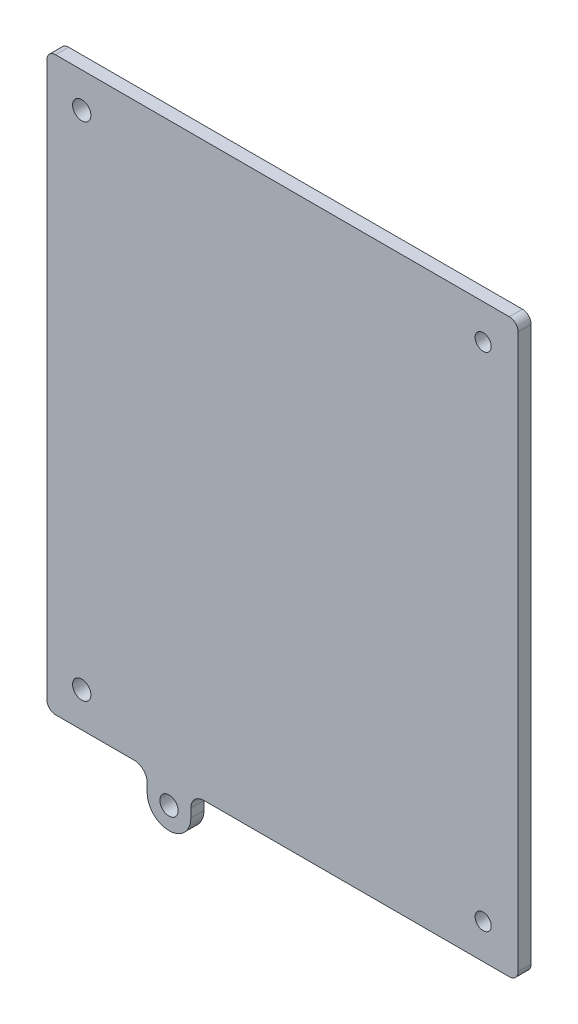
SolidWorks part; units mm, degrees
material "6061-T6 Black anodised"
ref_plane "Front Plane" through (0, 0, 0) normal (0, 0, 1) x (1, 0, 0)
ref_plane "Top Plane" through (0, 0, 0) normal (0, 1, 0) x (1, 0, 0)
ref_plane "Right Plane" through (0, 0, 0) normal (1, 0, 0) x (0, 0, -1)
sketch "Model" plane through (0, 0, 0) normal (0, 0, 1) x (1, 0, 0)
  line L0 (104.1673, 32.1811) -> (4.1672, 32.1811)
  line L1 (104.1673, 155.1806) -> (104.1673, 32.1811)
  line L2 (4.1672, 155.1806) -> (104.1673, 155.1806)
  line L3 (4.1672, 32.1811) -> (4.1672, 155.1806)
  line L4 (44.9158, 146.4259) -> (47.4224, 146.4259)
  line L5 (47.4224, 146.4259) -> (47.4224, 148.9326)
  line L6 (47.4224, 148.9326) -> (44.9158, 148.9326)
  line L7 (44.9158, 148.9326) -> (44.9158, 146.4259)
  line L8 (77.4127, 147.4278) -> (79.9193, 147.4278)
  line L9 (79.9193, 147.4278) -> (79.9193, 149.9344)
  line L10 (79.9193, 149.9344) -> (77.4127, 149.9344)
  line L11 (77.4127, 149.9344) -> (77.4127, 147.4278)
  line L12 (6.3266, 141.9721) -> (8.3592, 141.9721)
  line L13 (8.3592, 141.9721) -> (8.3592, 144.0047)
  line L14 (8.3592, 144.0047) -> (6.3266, 144.0047)
  line L15 (6.3266, 144.0047) -> (6.3266, 141.9721)
  line L16 (6.3266, 121.6529) -> (8.3592, 121.6529)
  line L17 (8.3592, 121.6529) -> (8.3592, 123.6855)
  line L18 (8.3592, 123.6855) -> (6.3266, 123.6855)
  line L19 (6.3266, 123.6855) -> (6.3266, 121.6529)
  line L20 (6.3266, 101.3324) -> (8.3592, 101.3324)
  line L21 (8.3592, 101.3324) -> (8.3592, 103.365)
  line L22 (8.3592, 103.365) -> (6.3266, 103.365)
  line L23 (6.3266, 103.365) -> (6.3266, 101.3324)
  line L24 (6.3266, 81.0118) -> (8.3592, 81.0118)
  line L25 (8.3592, 81.0118) -> (8.3592, 83.0444)
  line L26 (8.3592, 83.0444) -> (6.3266, 83.0444)
  line L27 (6.3266, 83.0444) -> (6.3266, 81.0118)
  line L28 (6.3266, 60.6927) -> (8.3592, 60.6927)
  line L29 (8.3592, 60.6927) -> (8.3592, 62.7253)
  line L30 (8.3592, 62.7253) -> (6.3266, 62.7253)
  line L31 (6.3266, 62.7253) -> (6.3266, 60.6927)
  line L32 (85.9221, 148.4144) -> (87.9547, 148.4144)
  line L33 (87.9547, 148.4144) -> (87.9547, 150.447)
  line L34 (87.9547, 150.447) -> (85.9221, 150.447)
  line L35 (85.9221, 150.447) -> (85.9221, 148.4144)
  line L36 (6.3266, 50.5324) -> (8.3592, 50.5324)
  line L37 (8.3592, 50.5324) -> (8.3592, 52.565)
  line L38 (8.3592, 52.565) -> (6.3266, 52.565)
  line L39 (6.3266, 52.565) -> (6.3266, 50.5324)
  line L40 (6.3266, 42.9118) -> (8.3592, 42.9118)
  line L41 (8.3592, 42.9118) -> (8.3592, 44.9444)
  line L42 (8.3592, 44.9444) -> (6.3266, 44.9444)
  line L43 (6.3266, 44.9444) -> (6.3266, 42.9118)
  line L44 (52.8726, 50.0418) -> (54.3815, 50.0418)
  line L45 (54.3815, 50.0418) -> (54.3815, 51.5508)
  line L46 (54.3815, 51.5508) -> (52.8726, 51.5508)
  line L47 (52.8726, 51.5508) -> (52.8726, 50.0418)
  line L48 (58.4219, 130.1637) -> (60.4545, 130.1637)
  line L49 (60.4545, 130.1637) -> (60.4545, 132.1963)
  line L50 (60.4545, 132.1963) -> (58.4219, 132.1963)
  line L51 (58.4219, 132.1963) -> (58.4219, 130.1637)
  line L52 (97.8807, 141.1439) -> (99.9133, 141.1439)
  line L53 (99.9133, 141.1439) -> (99.9133, 143.1765)
  line L54 (99.9133, 143.1765) -> (97.8807, 143.1765)
  line L55 (97.8807, 143.1765) -> (97.8807, 141.1439)
  line L56 (48.438, 37.3046) -> (48.438, 37.0552)
  line L57 (49.9456, 37.0552) -> (49.9456, 37.3046)
  line L58 (52.8877, 37.3046) -> (52.8877, 37.0552)
  line L59 (54.3967, 37.0552) -> (54.3967, 37.3046)
  line L60 (54.3126, 34.0993) -> (54.3126, 33.8995)
  line L61 (56.7201, 33.8995) -> (56.7201, 34.0993)
  line L62 (46.1133, 34.0993) -> (46.1133, 33.8995)
  line L63 (48.5207, 33.8995) -> (48.5207, 34.0993)
  line L64 (82.9607, 49.0165) -> (84.9933, 49.0165)
  line L65 (84.9933, 49.0165) -> (84.9933, 51.0492)
  line L66 (84.9933, 51.0492) -> (82.9607, 51.0492)
  line L67 (82.9607, 51.0492) -> (82.9607, 49.0165)
  line L68 (29.8828, 70.9163) -> (31.9154, 70.9163)
  line L69 (31.9154, 70.9163) -> (31.9154, 72.9489)
  line L70 (31.9154, 72.9489) -> (29.8828, 72.9489)
  line L71 (29.8828, 72.9489) -> (29.8828, 70.9163)
  line L72 (29.8828, 68.1658) -> (31.9154, 68.1658)
  line L73 (31.9154, 68.1658) -> (31.9154, 70.1984)
  line L74 (31.9154, 70.1984) -> (29.8828, 70.1984)
  line L75 (29.8828, 70.1984) -> (29.8828, 68.1658)
  line L76 (29.8828, 108.6649) -> (31.9154, 108.6649)
  line L77 (31.9154, 108.6649) -> (31.9154, 110.6975)
  line L78 (31.9154, 110.6975) -> (29.8828, 110.6975)
  line L79 (29.8828, 110.6975) -> (29.8828, 108.6649)
  line L80 (29.8828, 111.4141) -> (31.9154, 111.4141)
  line L81 (31.9154, 111.4141) -> (31.9154, 113.4467)
  line L82 (31.9154, 113.4467) -> (29.8828, 113.4467)
  line L83 (29.8828, 113.4467) -> (29.8828, 111.4141)
  line L84 (29.8828, 91.1652) -> (31.9154, 91.1652)
  line L85 (31.9154, 91.1652) -> (31.9154, 93.1978)
  line L86 (31.9154, 93.1978) -> (29.8828, 93.1978)
  line L87 (29.8828, 93.1978) -> (29.8828, 91.1652)
  line L88 (29.8828, 88.4147) -> (31.9154, 88.4147)
  line L89 (31.9154, 88.4147) -> (31.9154, 90.4473)
  line L90 (31.9154, 90.4473) -> (29.8828, 90.4473)
  line L91 (29.8828, 90.4473) -> (29.8828, 88.4147)
  line L92 (29.8828, 128.6658) -> (31.9154, 128.6658)
  line L93 (31.9154, 128.6658) -> (31.9154, 130.6984)
  line L94 (31.9154, 130.6984) -> (29.8828, 130.6984)
  line L95 (29.8828, 130.6984) -> (29.8828, 128.6658)
  line L96 (29.8828, 131.4163) -> (31.9154, 131.4163)
  line L97 (31.9154, 131.4163) -> (31.9154, 133.4489)
  line L98 (31.9154, 133.4489) -> (29.8828, 133.4489)
  line L99 (29.8828, 133.4489) -> (29.8828, 131.4163)
  line L100 (48.1611, 135.1453) -> (50.1937, 135.1453)
  line L101 (50.1937, 135.1453) -> (50.1937, 137.1779)
  line L102 (50.1937, 137.1779) -> (48.1611, 137.1779)
  line L103 (48.1611, 137.1779) -> (48.1611, 135.1453)
  line L104 (11.4074, 121.6529) -> (13.44, 121.6529)
  line L105 (13.44, 121.6529) -> (13.44, 123.6855)
  line L106 (13.44, 123.6855) -> (11.4074, 123.6855)
  line L107 (11.4074, 123.6855) -> (11.4074, 121.6529)
  line L108 (104.1673, 32.1811) -> (4.1672, 32.1811)
  line L109 (104.1673, 155.1806) -> (104.1673, 32.1811)
  line L110 (4.1672, 155.1806) -> (104.1673, 155.1806)
  line L111 (4.1672, 32.1811) -> (4.1672, 155.1806)
  spline S0 degree 3 poles (55.1711, 147.6799) (55.1711, 149.685) (52.1643, 149.685) (52.1643, 147.6799) knots 0 0 0 0 1 1 1 1
  spline S1 degree 3 poles (52.1643, 147.6799) (52.1643, 145.6749) (55.1711, 145.6749) (55.1711, 147.6799) knots 0 0 0 0 1 1 1 1
  spline S2 degree 3 poles (75.1706, 148.6804) (75.1706, 150.6854) (72.1637, 150.6854) (72.1637, 148.6804) knots 0 0 0 0 1 1 1 1
  spline S3 degree 3 poles (72.1637, 148.6804) (72.1637, 146.6754) (75.1706, 146.6754) (75.1706, 148.6804) knots 0 0 0 0 1 1 1 1
  spline S4 degree 3 poles (8.3592, 140.448) (8.3592, 141.8026) (6.3266, 141.8026) (6.3266, 140.448) knots 0 0 0 0 1 1 1 1
  spline S5 degree 3 poles (6.3266, 140.448) (6.3266, 139.0934) (8.3592, 139.0934) (8.3592, 140.448) knots 0 0 0 0 1 1 1 1
  spline S6 degree 3 poles (8.3592, 137.9083) (8.3592, 139.2629) (6.3266, 139.2629) (6.3266, 137.9083) knots 0 0 0 0 1 1 1 1
  spline S7 degree 3 poles (6.3266, 137.9083) (6.3266, 136.5537) (8.3592, 136.5537) (8.3592, 137.9083) knots 0 0 0 0 1 1 1 1
  spline S8 degree 3 poles (8.3592, 135.3686) (8.3592, 136.7232) (6.3266, 136.7232) (6.3266, 135.3686) knots 0 0 0 0 1 1 1 1
  spline S9 degree 3 poles (6.3266, 135.3686) (6.3266, 134.0139) (8.3592, 134.0139) (8.3592, 135.3686) knots 0 0 0 0 1 1 1 1
  spline S10 degree 3 poles (8.3592, 132.8288) (8.3592, 134.1834) (6.3266, 134.1834) (6.3266, 132.8288) knots 0 0 0 0 1 1 1 1
  spline S11 degree 3 poles (6.3266, 132.8288) (6.3266, 131.4742) (8.3592, 131.4742) (8.3592, 132.8288) knots 0 0 0 0 1 1 1 1
  spline S12 degree 3 poles (8.3592, 130.2891) (8.3592, 131.6437) (6.3266, 131.6437) (6.3266, 130.2891) knots 0 0 0 0 1 1 1 1
  spline S13 degree 3 poles (6.3266, 130.2891) (6.3266, 128.9331) (8.3592, 128.9331) (8.3592, 130.2891) knots 0 0 0 0 1 1 1 1
  spline S14 degree 3 poles (8.3592, 127.748) (8.3592, 129.1026) (6.3266, 129.1026) (6.3266, 127.748) knots 0 0 0 0 1 1 1 1
  spline S15 degree 3 poles (6.3266, 127.748) (6.3266, 126.3934) (8.3592, 126.3934) (8.3592, 127.748) knots 0 0 0 0 1 1 1 1
  spline S16 degree 3 poles (8.3592, 120.1288) (8.3592, 121.4834) (6.3266, 121.4834) (6.3266, 120.1288) knots 0 0 0 0 1 1 1 1
  spline S17 degree 3 poles (6.3266, 120.1288) (6.3266, 118.7742) (8.3592, 118.7742) (8.3592, 120.1288) knots 0 0 0 0 1 1 1 1
  spline S18 degree 3 poles (8.3592, 117.5891) (8.3592, 118.9437) (6.3266, 118.9437) (6.3266, 117.5891) knots 0 0 0 0 1 1 1 1
  spline S19 degree 3 poles (6.3266, 117.5891) (6.3266, 116.2331) (8.3592, 116.2331) (8.3592, 117.5891) knots 0 0 0 0 1 1 1 1
  spline S20 degree 3 poles (8.3592, 115.048) (8.3592, 116.4026) (6.3266, 116.4026) (6.3266, 115.048) knots 0 0 0 0 1 1 1 1
  spline S21 degree 3 poles (6.3266, 115.048) (6.3266, 113.6934) (8.3592, 113.6934) (8.3592, 115.048) knots 0 0 0 0 1 1 1 1
  spline S22 degree 3 poles (8.3592, 112.5083) (8.3592, 113.8629) (6.3266, 113.8629) (6.3266, 112.5083) knots 0 0 0 0 1 1 1 1
  spline S23 degree 3 poles (6.3266, 112.5083) (6.3266, 111.1537) (8.3592, 111.1537) (8.3592, 112.5083) knots 0 0 0 0 1 1 1 1
  spline S24 degree 3 poles (8.3592, 109.9686) (8.3592, 111.3232) (6.3266, 111.3232) (6.3266, 109.9686) knots 0 0 0 0 1 1 1 1
  spline S25 degree 3 poles (6.3266, 109.9686) (6.3266, 108.6139) (8.3592, 108.6139) (8.3592, 109.9686) knots 0 0 0 0 1 1 1 1
  spline S26 degree 3 poles (8.3592, 107.4288) (8.3592, 108.7834) (6.3266, 108.7834) (6.3266, 107.4288) knots 0 0 0 0 1 1 1 1
  spline S27 degree 3 poles (6.3266, 107.4288) (6.3266, 106.0742) (8.3592, 106.0742) (8.3592, 107.4288) knots 0 0 0 0 1 1 1 1
  spline S28 degree 3 poles (8.3592, 99.8083) (8.3592, 101.1629) (6.3266, 101.1629) (6.3266, 99.8083) knots 0 0 0 0 1 1 1 1
  spline S29 degree 3 poles (6.3266, 99.8083) (6.3266, 98.4537) (8.3592, 98.4537) (8.3592, 99.8083) knots 0 0 0 0 1 1 1 1
  spline S30 degree 3 poles (8.3592, 97.2686) (8.3592, 98.6232) (6.3266, 98.6232) (6.3266, 97.2686) knots 0 0 0 0 1 1 1 1
  spline S31 degree 3 poles (6.3266, 97.2686) (6.3266, 95.9139) (8.3592, 95.9139) (8.3592, 97.2686) knots 0 0 0 0 1 1 1 1
  spline S32 degree 3 poles (8.3592, 94.7288) (8.3592, 96.0834) (6.3266, 96.0834) (6.3266, 94.7288) knots 0 0 0 0 1 1 1 1
  spline S33 degree 3 poles (6.3266, 94.7288) (6.3266, 93.3742) (8.3592, 93.3742) (8.3592, 94.7288) knots 0 0 0 0 1 1 1 1
  spline S34 degree 3 poles (8.3592, 92.1891) (8.3592, 93.5437) (6.3266, 93.5437) (6.3266, 92.1891) knots 0 0 0 0 1 1 1 1
  spline S35 degree 3 poles (6.3266, 92.1891) (6.3266, 90.8331) (8.3592, 90.8331) (8.3592, 92.1891) knots 0 0 0 0 1 1 1 1
  spline S36 degree 3 poles (8.3592, 89.648) (8.3592, 91.0026) (6.3266, 91.0026) (6.3266, 89.648) knots 0 0 0 0 1 1 1 1
  spline S37 degree 3 poles (6.3266, 89.648) (6.3266, 88.2934) (8.3592, 88.2934) (8.3592, 89.648) knots 0 0 0 0 1 1 1 1
  spline S38 degree 3 poles (8.3592, 87.1083) (8.3592, 88.4629) (6.3266, 88.4629) (6.3266, 87.1083) knots 0 0 0 0 1 1 1 1
  spline S39 degree 3 poles (6.3266, 87.1083) (6.3266, 85.7537) (8.3592, 85.7537) (8.3592, 87.1083) knots 0 0 0 0 1 1 1 1
  spline S40 degree 3 poles (8.3592, 79.4891) (8.3592, 80.8437) (6.3266, 80.8437) (6.3266, 79.4891) knots 0 0 0 0 1 1 1 1
  spline S41 degree 3 poles (6.3266, 79.4891) (6.3266, 78.1331) (8.3592, 78.1331) (8.3592, 79.4891) knots 0 0 0 0 1 1 1 1
  spline S42 degree 3 poles (8.3592, 76.948) (8.3592, 78.3026) (6.3266, 78.3026) (6.3266, 76.948) knots 0 0 0 0 1 1 1 1
  spline S43 degree 3 poles (6.3266, 76.948) (6.3266, 75.5934) (8.3592, 75.5934) (8.3592, 76.948) knots 0 0 0 0 1 1 1 1
  spline S44 degree 3 poles (8.3592, 74.4083) (8.3592, 75.7629) (6.3266, 75.7629) (6.3266, 74.4083) knots 0 0 0 0 1 1 1 1
  spline S45 degree 3 poles (6.3266, 74.4083) (6.3266, 73.0537) (8.3592, 73.0537) (8.3592, 74.4083) knots 0 0 0 0 1 1 1 1
  spline S46 degree 3 poles (8.3592, 71.8685) (8.3592, 73.2232) (6.3266, 73.2232) (6.3266, 71.8685) knots 0 0 0 0 1 1 1 1
  spline S47 degree 3 poles (6.3266, 71.8685) (6.3266, 70.5139) (8.3592, 70.5139) (8.3592, 71.8685) knots 0 0 0 0 1 1 1 1
  spline S48 degree 3 poles (8.3592, 69.3288) (8.3592, 70.6834) (6.3266, 70.6834) (6.3266, 69.3288) knots 0 0 0 0 1 1 1 1
  spline S49 degree 3 poles (6.3266, 69.3288) (6.3266, 67.9742) (8.3592, 67.9742) (8.3592, 69.3288) knots 0 0 0 0 1 1 1 1
  spline S50 degree 3 poles (8.3592, 66.7891) (8.3592, 68.1437) (6.3266, 68.1437) (6.3266, 66.7891) knots 0 0 0 0 1 1 1 1
  spline S51 degree 3 poles (6.3266, 66.7891) (6.3266, 65.4331) (8.3592, 65.4331) (8.3592, 66.7891) knots 0 0 0 0 1 1 1 1
  spline S52 degree 3 poles (8.3592, 59.1686) (8.3592, 60.5232) (6.3266, 60.5232) (6.3266, 59.1686) knots 0 0 0 0 1 1 1 1
  spline S53 degree 3 poles (6.3266, 59.1686) (6.3266, 57.8139) (8.3592, 57.8139) (8.3592, 59.1686) knots 0 0 0 0 1 1 1 1
  spline S54 degree 3 poles (8.3592, 56.6288) (8.3592, 57.9834) (6.3266, 57.9834) (6.3266, 56.6288) knots 0 0 0 0 1 1 1 1
  spline S55 degree 3 poles (6.3266, 56.6288) (6.3266, 55.2742) (8.3592, 55.2742) (8.3592, 56.6288) knots 0 0 0 0 1 1 1 1
  spline S56 degree 3 poles (8.3592, 54.0891) (8.3592, 55.4437) (6.3266, 55.4437) (6.3266, 54.0891) knots 0 0 0 0 1 1 1 1
  spline S57 degree 3 poles (6.3266, 54.0891) (6.3266, 52.7331) (8.3592, 52.7331) (8.3592, 54.0891) knots 0 0 0 0 1 1 1 1
  spline S58 degree 3 poles (85.4149, 149.4301) (85.4149, 150.7847) (83.3823, 150.7847) (83.3823, 149.4301) knots 0 0 0 0 1 1 1 1
  spline S59 degree 3 poles (83.3823, 149.4301) (83.3823, 148.0754) (85.4149, 148.0754) (85.4149, 149.4301) knots 0 0 0 0 1 1 1 1
  spline S60 degree 3 poles (8.3592, 49.0083) (8.3592, 50.3629) (6.3266, 50.3629) (6.3266, 49.0083) knots 0 0 0 0 1 1 1 1
  spline S61 degree 3 poles (6.3266, 49.0083) (6.3266, 47.6537) (8.3592, 47.6537) (8.3592, 49.0083) knots 0 0 0 0 1 1 1 1
  spline S62 degree 3 poles (8.3592, 41.3891) (8.3592, 42.7437) (6.3266, 42.7437) (6.3266, 41.3891) knots 0 0 0 0 1 1 1 1
  spline S63 degree 3 poles (6.3266, 41.3891) (6.3266, 40.0331) (8.3592, 40.0331) (8.3592, 41.3891) knots 0 0 0 0 1 1 1 1
  spline S64 degree 3 poles (54.3815, 52.0661) (54.3815, 53.0721) (52.8726, 53.0721) (52.8726, 52.0661) knots 0 0 0 0 1 1 1 1
  spline S65 degree 3 poles (52.8726, 52.0661) (52.8726, 51.0602) (54.3815, 51.0602) (54.3815, 52.0661) knots 0 0 0 0 1 1 1 1
  spline S66 degree 3 poles (55.6507, 50.797) (55.6507, 51.8029) (54.1417, 51.8029) (54.1417, 50.797) knots 0 0 0 0 1 1 1 1
  spline S67 degree 3 poles (54.1417, 50.797) (54.1417, 49.791) (55.6507, 49.791) (55.6507, 50.797) knots 0 0 0 0 1 1 1 1
  spline S68 degree 3 poles (55.6507, 52.0661) (55.6507, 53.0721) (54.1417, 53.0721) (54.1417, 52.0661) knots 0 0 0 0 1 1 1 1
  spline S69 degree 3 poles (54.1417, 52.0661) (54.1417, 51.0602) (55.6507, 51.0602) (55.6507, 52.0661) knots 0 0 0 0 1 1 1 1
  spline S70 degree 3 poles (56.9212, 50.797) (56.9212, 51.8029) (55.4123, 51.8029) (55.4123, 50.797) knots 0 0 0 0 1 1 1 1
  spline S71 degree 3 poles (55.4123, 50.797) (55.4123, 49.791) (56.9212, 49.791) (56.9212, 50.797) knots 0 0 0 0 1 1 1 1
  spline S72 degree 3 poles (56.9212, 52.0661) (56.9212, 53.0721) (55.4123, 53.0721) (55.4123, 52.0661) knots 0 0 0 0 1 1 1 1
  spline S73 degree 3 poles (55.4123, 52.0661) (55.4123, 51.0602) (56.9212, 51.0602) (56.9212, 52.0661) knots 0 0 0 0 1 1 1 1
  spline S74 degree 3 poles (58.1904, 50.797) (58.1904, 51.8029) (56.6828, 51.8029) (56.6828, 50.797) knots 0 0 0 0 1 1 1 1
  spline S75 degree 3 poles (56.6828, 50.797) (56.6828, 49.791) (58.1904, 49.791) (58.1904, 50.797) knots 0 0 0 0 1 1 1 1
  spline S76 degree 3 poles (58.1904, 52.0661) (58.1904, 53.0721) (56.6828, 53.0721) (56.6828, 52.0661) knots 0 0 0 0 1 1 1 1
  spline S77 degree 3 poles (56.6828, 52.0661) (56.6828, 51.0602) (58.1904, 51.0602) (58.1904, 52.0661) knots 0 0 0 0 1 1 1 1
  spline S78 degree 3 poles (59.461, 50.797) (59.461, 51.8029) (57.952, 51.8029) (57.952, 50.797) knots 0 0 0 0 1 1 1 1
  spline S79 degree 3 poles (57.952, 50.797) (57.952, 49.791) (59.461, 49.791) (59.461, 50.797) knots 0 0 0 0 1 1 1 1
  spline S80 degree 3 poles (59.461, 52.0661) (59.461, 53.0721) (57.952, 53.0721) (57.952, 52.0661) knots 0 0 0 0 1 1 1 1
  spline S81 degree 3 poles (57.952, 52.0661) (57.952, 51.0602) (59.461, 51.0602) (59.461, 52.0661) knots 0 0 0 0 1 1 1 1
  spline S82 degree 3 poles (57.9148, 131.1793) (57.9148, 132.5353) (55.8822, 132.5353) (55.8822, 131.1793) knots 0 0 0 0 1 1 1 1
  spline S83 degree 3 poles (55.8822, 131.1793) (55.8822, 129.8247) (57.9148, 129.8247) (57.9148, 131.1793) knots 0 0 0 0 1 1 1 1
  spline S84 degree 3 poles (63.2437, 36.9311) (63.2437, 37.9371) (61.7347, 37.9371) (61.7347, 36.9311) knots 0 0 0 0 1 1 1 1
  spline S85 degree 3 poles (61.7347, 36.9311) (61.7347, 35.9252) (63.2437, 35.9252) (63.2437, 36.9311) knots 0 0 0 0 1 1 1 1
  spline S86 degree 3 poles (71.2239, 36.9311) (71.2239, 37.9371) (69.715, 37.9371) (69.715, 36.9311) knots 0 0 0 0 1 1 1 1
  spline S87 degree 3 poles (69.715, 36.9311) (69.715, 35.9252) (71.2239, 35.9252) (71.2239, 36.9311) knots 0 0 0 0 1 1 1 1
  spline S88 degree 3 poles (102.453, 142.1609) (102.453, 143.5155) (100.4204, 143.5155) (100.4204, 142.1609) knots 0 0 0 0 1 1 1 1
  spline S89 degree 3 poles (100.4204, 142.1609) (100.4204, 140.8063) (102.453, 140.8063) (102.453, 142.1609) knots 0 0 0 0 1 1 1 1
  spline S90 degree 3 poles (99.9133, 129.4609) (99.9133, 130.8155) (97.8807, 130.8155) (97.8807, 129.4609) knots 0 0 0 0 1 1 1 1
  spline S91 degree 3 poles (97.8807, 129.4609) (97.8807, 128.1063) (99.9133, 128.1063) (99.9133, 129.4609) knots 0 0 0 0 1 1 1 1
  spline S92 degree 3 poles (102.453, 139.6198) (102.453, 140.9744) (100.4204, 140.9744) (100.4204, 139.6198) knots 0 0 0 0 1 1 1 1
  spline S93 degree 3 poles (100.4204, 139.6198) (100.4204, 138.2652) (102.453, 138.2652) (102.453, 139.6198) knots 0 0 0 0 1 1 1 1
  spline S94 degree 3 poles (99.9133, 126.9198) (99.9133, 128.2744) (97.8807, 128.2744) (97.8807, 126.9198) knots 0 0 0 0 1 1 1 1
  spline S95 degree 3 poles (97.8807, 126.9198) (97.8807, 125.5652) (99.9133, 125.5652) (99.9133, 126.9198) knots 0 0 0 0 1 1 1 1
  spline S96 degree 3 poles (102.453, 137.0801) (102.453, 138.4347) (100.4204, 138.4347) (100.4204, 137.0801) knots 0 0 0 0 1 1 1 1
  spline S97 degree 3 poles (100.4204, 137.0801) (100.4204, 135.7255) (102.453, 135.7255) (102.453, 137.0801) knots 0 0 0 0 1 1 1 1
  spline S98 degree 3 poles (99.9133, 124.3801) (99.9133, 125.7347) (97.8807, 125.7347) (97.8807, 124.3801) knots 0 0 0 0 1 1 1 1
  spline S99 degree 3 poles (97.8807, 124.3801) (97.8807, 123.0255) (99.9133, 123.0255) (99.9133, 124.3801) knots 0 0 0 0 1 1 1 1
  spline S100 degree 3 poles (102.453, 134.5403) (102.453, 135.895) (100.4204, 135.895) (100.4204, 134.5403) knots 0 0 0 0 1 1 1 1
  spline S101 degree 3 poles (100.4204, 134.5403) (100.4204, 133.1857) (102.453, 133.1857) (102.453, 134.5403) knots 0 0 0 0 1 1 1 1
  spline S102 degree 3 poles (99.9133, 121.8404) (99.9133, 123.195) (97.8807, 123.195) (97.8807, 121.8404) knots 0 0 0 0 1 1 1 1
  spline S103 degree 3 poles (97.8807, 121.8404) (97.8807, 120.4857) (99.9133, 120.4857) (99.9133, 121.8404) knots 0 0 0 0 1 1 1 1
  spline S104 degree 3 poles (102.453, 132.0006) (102.453, 133.3552) (100.4204, 133.3552) (100.4204, 132.0006) knots 0 0 0 0 1 1 1 1
  spline S105 degree 3 poles (100.4204, 132.0006) (100.4204, 130.646) (102.453, 130.646) (102.453, 132.0006) knots 0 0 0 0 1 1 1 1
  spline S106 degree 3 poles (99.9133, 119.3006) (99.9133, 120.6552) (97.8807, 120.6552) (97.8807, 119.3006) knots 0 0 0 0 1 1 1 1
  spline S107 degree 3 poles (97.8807, 119.3006) (97.8807, 117.946) (99.9133, 117.946) (99.9133, 119.3006) knots 0 0 0 0 1 1 1 1
  spline S108 degree 3 poles (102.453, 129.4609) (102.453, 130.8155) (100.4204, 130.8155) (100.4204, 129.4609) knots 0 0 0 0 1 1 1 1
  spline S109 degree 3 poles (100.4204, 129.4609) (100.4204, 128.1063) (102.453, 128.1063) (102.453, 129.4609) knots 0 0 0 0 1 1 1 1
  spline S110 degree 3 poles (99.9133, 116.7609) (99.9133, 118.1155) (97.8807, 118.1155) (97.8807, 116.7609) knots 0 0 0 0 1 1 1 1
  spline S111 degree 3 poles (97.8807, 116.7609) (97.8807, 115.4063) (99.9133, 115.4063) (99.9133, 116.7609) knots 0 0 0 0 1 1 1 1
  spline S112 degree 3 poles (102.453, 126.9198) (102.453, 128.2744) (100.4204, 128.2744) (100.4204, 126.9198) knots 0 0 0 0 1 1 1 1
  spline S113 degree 3 poles (100.4204, 126.9198) (100.4204, 125.5652) (102.453, 125.5652) (102.453, 126.9198) knots 0 0 0 0 1 1 1 1
  spline S114 degree 3 poles (99.9133, 114.2198) (99.9133, 115.5744) (97.8807, 115.5744) (97.8807, 114.2198) knots 0 0 0 0 1 1 1 1
  spline S115 degree 3 poles (97.8807, 114.2198) (97.8807, 112.8652) (99.9133, 112.8652) (99.9133, 114.2198) knots 0 0 0 0 1 1 1 1
  spline S116 degree 3 poles (102.453, 124.3801) (102.453, 125.7347) (100.4204, 125.7347) (100.4204, 124.3801) knots 0 0 0 0 1 1 1 1
  spline S117 degree 3 poles (100.4204, 124.3801) (100.4204, 123.0255) (102.453, 123.0255) (102.453, 124.3801) knots 0 0 0 0 1 1 1 1
  spline S118 degree 3 poles (99.9133, 111.6801) (99.9133, 113.0347) (97.8807, 113.0347) (97.8807, 111.6801) knots 0 0 0 0 1 1 1 1
  spline S119 degree 3 poles (97.8807, 111.6801) (97.8807, 110.3255) (99.9133, 110.3255) (99.9133, 111.6801) knots 0 0 0 0 1 1 1 1
  spline S120 degree 3 poles (102.453, 121.8404) (102.453, 123.195) (100.4204, 123.195) (100.4204, 121.8404) knots 0 0 0 0 1 1 1 1
  spline S121 degree 3 poles (100.4204, 121.8404) (100.4204, 120.4857) (102.453, 120.4857) (102.453, 121.8404) knots 0 0 0 0 1 1 1 1
  spline S122 degree 3 poles (99.9133, 109.1404) (99.9133, 110.495) (97.8807, 110.495) (97.8807, 109.1404) knots 0 0 0 0 1 1 1 1
  spline S123 degree 3 poles (97.8807, 109.1404) (97.8807, 107.7857) (99.9133, 107.7857) (99.9133, 109.1404) knots 0 0 0 0 1 1 1 1
  spline S124 degree 3 poles (102.453, 119.3006) (102.453, 120.6552) (100.4204, 120.6552) (100.4204, 119.3006) knots 0 0 0 0 1 1 1 1
  spline S125 degree 3 poles (100.4204, 119.3006) (100.4204, 117.946) (102.453, 117.946) (102.453, 119.3006) knots 0 0 0 0 1 1 1 1
  spline S126 degree 3 poles (99.9133, 106.6006) (99.9133, 107.9552) (97.8807, 107.9552) (97.8807, 106.6006) knots 0 0 0 0 1 1 1 1
  spline S127 degree 3 poles (97.8807, 106.6006) (97.8807, 105.246) (99.9133, 105.246) (99.9133, 106.6006) knots 0 0 0 0 1 1 1 1
  spline S128 degree 3 poles (102.453, 116.7609) (102.453, 118.1155) (100.4204, 118.1155) (100.4204, 116.7609) knots 0 0 0 0 1 1 1 1
  spline S129 degree 3 poles (100.4204, 116.7609) (100.4204, 115.4063) (102.453, 115.4063) (102.453, 116.7609) knots 0 0 0 0 1 1 1 1
  spline S130 degree 3 poles (99.9133, 104.0609) (99.9133, 105.4155) (97.8807, 105.4155) (97.8807, 104.0609) knots 0 0 0 0 1 1 1 1
  spline S131 degree 3 poles (97.8807, 104.0609) (97.8807, 102.7063) (99.9133, 102.7063) (99.9133, 104.0609) knots 0 0 0 0 1 1 1 1
  spline S132 degree 3 poles (102.453, 114.2198) (102.453, 115.5744) (100.4204, 115.5744) (100.4204, 114.2198) knots 0 0 0 0 1 1 1 1
  spline S133 degree 3 poles (100.4204, 114.2198) (100.4204, 112.8652) (102.453, 112.8652) (102.453, 114.2198) knots 0 0 0 0 1 1 1 1
  spline S134 degree 3 poles (102.453, 111.6801) (102.453, 113.0347) (100.4204, 113.0347) (100.4204, 111.6801) knots 0 0 0 0 1 1 1 1
  spline S135 degree 3 poles (100.4204, 111.6801) (100.4204, 110.3255) (102.453, 110.3255) (102.453, 111.6801) knots 0 0 0 0 1 1 1 1
  spline S136 degree 3 poles (99.9133, 101.5198) (99.9133, 102.8744) (97.8807, 102.8744) (97.8807, 101.5198) knots 0 0 0 0 1 1 1 1
  spline S137 degree 3 poles (97.8807, 101.5198) (97.8807, 100.1652) (99.9133, 100.1652) (99.9133, 101.5198) knots 0 0 0 0 1 1 1 1
  spline S138 degree 3 poles (102.453, 109.1404) (102.453, 110.495) (100.4204, 110.495) (100.4204, 109.1404) knots 0 0 0 0 1 1 1 1
  spline S139 degree 3 poles (100.4204, 109.1404) (100.4204, 107.7857) (102.453, 107.7857) (102.453, 109.1404) knots 0 0 0 0 1 1 1 1
  spline S140 degree 3 poles (102.453, 104.0609) (102.453, 105.4155) (100.4204, 105.4155) (100.4204, 104.0609) knots 0 0 0 0 1 1 1 1
  spline S141 degree 3 poles (100.4204, 104.0609) (100.4204, 102.7063) (102.453, 102.7063) (102.453, 104.0609) knots 0 0 0 0 1 1 1 1
  spline S142 degree 3 poles (102.453, 101.5198) (102.453, 102.8744) (100.4204, 102.8744) (100.4204, 101.5198) knots 0 0 0 0 1 1 1 1
  spline S143 degree 3 poles (100.4204, 101.5198) (100.4204, 100.1652) (102.453, 100.1652) (102.453, 101.5198) knots 0 0 0 0 1 1 1 1
  spline S144 degree 3 poles (102.453, 98.9801) (102.453, 100.3347) (100.4204, 100.3347) (100.4204, 98.9801) knots 0 0 0 0 1 1 1 1
  spline S145 degree 3 poles (100.4204, 98.9801) (100.4204, 97.6255) (102.453, 97.6255) (102.453, 98.9801) knots 0 0 0 0 1 1 1 1
  spline S146 degree 3 poles (102.453, 96.4404) (102.453, 97.795) (100.4204, 97.795) (100.4204, 96.4404) knots 0 0 0 0 1 1 1 1
  spline S147 degree 3 poles (100.4204, 96.4404) (100.4204, 95.0857) (102.453, 95.0857) (102.453, 96.4404) knots 0 0 0 0 1 1 1 1
  spline S148 degree 3 poles (99.9133, 98.9801) (99.9133, 100.3347) (97.8807, 100.3347) (97.8807, 98.9801) knots 0 0 0 0 1 1 1 1
  spline S149 degree 3 poles (97.8807, 98.9801) (97.8807, 97.6255) (99.9133, 97.6255) (99.9133, 98.9801) knots 0 0 0 0 1 1 1 1
  spline S150 degree 3 poles (99.9133, 96.4404) (99.9133, 97.795) (97.8807, 97.795) (97.8807, 96.4404) knots 0 0 0 0 1 1 1 1
  spline S151 degree 3 poles (97.8807, 96.4404) (97.8807, 95.0857) (99.9133, 95.0857) (99.9133, 96.4404) knots 0 0 0 0 1 1 1 1
  spline S152 degree 3 poles (99.9133, 139.6198) (99.9133, 140.9744) (97.8807, 140.9744) (97.8807, 139.6198) knots 0 0 0 0 1 1 1 1
  spline S153 degree 3 poles (97.8807, 139.6198) (97.8807, 138.2652) (99.9133, 138.2652) (99.9133, 139.6198) knots 0 0 0 0 1 1 1 1
  spline S154 degree 3 poles (99.9133, 137.0801) (99.9133, 138.4347) (97.8807, 138.4347) (97.8807, 137.0801) knots 0 0 0 0 1 1 1 1
  spline S155 degree 3 poles (97.8807, 137.0801) (97.8807, 135.7255) (99.9133, 135.7255) (99.9133, 137.0801) knots 0 0 0 0 1 1 1 1
  spline S156 degree 3 poles (99.9133, 134.5403) (99.9133, 135.895) (97.8807, 135.895) (97.8807, 134.5403) knots 0 0 0 0 1 1 1 1
  spline S157 degree 3 poles (97.8807, 134.5403) (97.8807, 133.1857) (99.9133, 133.1857) (99.9133, 134.5403) knots 0 0 0 0 1 1 1 1
  spline S158 degree 3 poles (99.9133, 132.0006) (99.9133, 133.3552) (97.8807, 133.3552) (97.8807, 132.0006) knots 0 0 0 0 1 1 1 1
  spline S159 degree 3 poles (97.8807, 132.0006) (97.8807, 130.646) (99.9133, 130.646) (99.9133, 132.0006) knots 0 0 0 0 1 1 1 1
  spline S160 degree 3 poles (99.9133, 93.9006) (99.9133, 95.2552) (97.8807, 95.2552) (97.8807, 93.9006) knots 0 0 0 0 1 1 1 1
  spline S161 degree 3 poles (97.8807, 93.9006) (97.8807, 92.546) (99.9133, 92.546) (99.9133, 93.9006) knots 0 0 0 0 1 1 1 1
  spline S162 degree 3 poles (102.453, 93.9006) (102.453, 95.2552) (100.4204, 95.2552) (100.4204, 93.9006) knots 0 0 0 0 1 1 1 1
  spline S163 degree 3 poles (100.4204, 93.9006) (100.4204, 92.546) (102.453, 92.546) (102.453, 93.9006) knots 0 0 0 0 1 1 1 1
  spline S164 degree 3 poles (102.453, 106.6006) (102.453, 107.9552) (100.4204, 107.9552) (100.4204, 106.6006) knots 0 0 0 0 1 1 1 1
  spline S165 degree 3 poles (100.4204, 106.6006) (100.4204, 105.246) (102.453, 105.246) (102.453, 106.6006) knots 0 0 0 0 1 1 1 1
  spline S166 degree 3 poles (99.9133, 91.3609) (99.9133, 92.7155) (97.8807, 92.7155) (97.8807, 91.3609) knots 0 0 0 0 1 1 1 1
  spline S167 degree 3 poles (97.8807, 91.3609) (97.8807, 90.0063) (99.9133, 90.0063) (99.9133, 91.3609) knots 0 0 0 0 1 1 1 1
  spline S168 degree 3 poles (102.453, 91.3609) (102.453, 92.7155) (100.4204, 92.7155) (100.4204, 91.3609) knots 0 0 0 0 1 1 1 1
  spline S169 degree 3 poles (100.4204, 91.3609) (100.4204, 90.0063) (102.453, 90.0063) (102.453, 91.3609) knots 0 0 0 0 1 1 1 1
  spline S170 degree 3 poles (99.9133, 88.8198) (99.9133, 90.1744) (97.8807, 90.1744) (97.8807, 88.8198) knots 0 0 0 0 1 1 1 1
  spline S171 degree 3 poles (97.8807, 88.8198) (97.8807, 87.4652) (99.9133, 87.4652) (99.9133, 88.8198) knots 0 0 0 0 1 1 1 1
  spline S172 degree 3 poles (102.453, 88.8198) (102.453, 90.1744) (100.4204, 90.1744) (100.4204, 88.8198) knots 0 0 0 0 1 1 1 1
  spline S173 degree 3 poles (100.4204, 88.8198) (100.4204, 87.4652) (102.453, 87.4652) (102.453, 88.8198) knots 0 0 0 0 1 1 1 1
  spline S174 degree 3 poles (99.9133, 86.2801) (99.9133, 87.6347) (97.8807, 87.6347) (97.8807, 86.2801) knots 0 0 0 0 1 1 1 1
  spline S175 degree 3 poles (97.8807, 86.2801) (97.8807, 84.9255) (99.9133, 84.9255) (99.9133, 86.2801) knots 0 0 0 0 1 1 1 1
  spline S176 degree 3 poles (102.453, 86.2801) (102.453, 87.6347) (100.4204, 87.6347) (100.4204, 86.2801) knots 0 0 0 0 1 1 1 1
  spline S177 degree 3 poles (100.4204, 86.2801) (100.4204, 84.9255) (102.453, 84.9255) (102.453, 86.2801) knots 0 0 0 0 1 1 1 1
  spline S178 degree 3 poles (99.9133, 83.7404) (99.9133, 85.095) (97.8807, 85.095) (97.8807, 83.7404) knots 0 0 0 0 1 1 1 1
  spline S179 degree 3 poles (97.8807, 83.7404) (97.8807, 82.3857) (99.9133, 82.3857) (99.9133, 83.7404) knots 0 0 0 0 1 1 1 1
  spline S180 degree 3 poles (102.453, 83.7404) (102.453, 85.095) (100.4204, 85.095) (100.4204, 83.7404) knots 0 0 0 0 1 1 1 1
  spline S181 degree 3 poles (100.4204, 83.7404) (100.4204, 82.3857) (102.453, 82.3857) (102.453, 83.7404) knots 0 0 0 0 1 1 1 1
  spline S182 degree 3 poles (99.9133, 81.2006) (99.9133, 82.5552) (97.8807, 82.5552) (97.8807, 81.2006) knots 0 0 0 0 1 1 1 1
  spline S183 degree 3 poles (97.8807, 81.2006) (97.8807, 79.846) (99.9133, 79.846) (99.9133, 81.2006) knots 0 0 0 0 1 1 1 1
  spline S184 degree 3 poles (102.453, 81.2006) (102.453, 82.5552) (100.4204, 82.5552) (100.4204, 81.2006) knots 0 0 0 0 1 1 1 1
  spline S185 degree 3 poles (100.4204, 81.2006) (100.4204, 79.846) (102.453, 79.846) (102.453, 81.2006) knots 0 0 0 0 1 1 1 1
  spline S186 degree 3 poles (49.9456, 37.3046) (49.9456, 38.3106) (48.438, 38.3106) (48.438, 37.3046) knots 0 0 0 0 1 1 1 1
  spline S187 degree 3 poles (48.438, 37.0552) (48.438, 36.0492) (49.9456, 36.0492) (49.9456, 37.0552) knots 0 0 0 0 1 1 1 1
  spline S188 degree 3 poles (54.3967, 37.3046) (54.3967, 38.3106) (52.8877, 38.3106) (52.8877, 37.3046) knots 0 0 0 0 1 1 1 1
  spline S189 degree 3 poles (52.8877, 37.0552) (52.8877, 36.0492) (54.3967, 36.0492) (54.3967, 37.0552) knots 0 0 0 0 1 1 1 1
  spline S190 degree 3 poles (56.7201, 34.0993) (56.7201, 35.7047) (54.3126, 35.7047) (54.3126, 34.0993) knots 0 0 0 0 1 1 1 1
  spline S191 degree 3 poles (54.3126, 33.8995) (54.3126, 32.2941) (56.7201, 32.2941) (56.7201, 33.8995) knots 0 0 0 0 1 1 1 1
  spline S192 degree 3 poles (48.5207, 34.0993) (48.5207, 35.7047) (46.1133, 35.7047) (46.1133, 34.0993) knots 0 0 0 0 1 1 1 1
  spline S193 degree 3 poles (46.1133, 33.8995) (46.1133, 32.2941) (48.5207, 32.2941) (48.5207, 33.8995) knots 0 0 0 0 1 1 1 1
  spline S194 degree 3 poles (54.4711, 34.0001) (54.4711, 34.9054) (53.1123, 34.9054) (53.1123, 34.0001) knots 0 0 0 0 1 1 1 1
  spline S195 degree 3 poles (53.1123, 34.0001) (53.1123, 33.0933) (54.4711, 33.0933) (54.4711, 34.0001) knots 0 0 0 0 1 1 1 1
  spline S196 degree 3 poles (49.721, 34.0001) (49.721, 34.9054) (48.3623, 34.9054) (48.3623, 34.0001) knots 0 0 0 0 1 1 1 1
  spline S197 degree 3 poles (48.3623, 34.0001) (48.3623, 33.0933) (49.721, 33.0933) (49.721, 34.0001) knots 0 0 0 0 1 1 1 1
  spline S198 degree 3 poles (84.606, 43.6822) (84.606, 46.2205) (80.7985, 46.2205) (80.7985, 43.6822) knots 0 0 0 0 1 1 1 1
  spline S199 degree 3 poles (80.7985, 43.6822) (80.7985, 41.1438) (84.606, 41.1438) (84.606, 43.6822) knots 0 0 0 0 1 1 1 1
  spline S200 degree 3 poles (96.0355, 43.6822) (96.0355, 46.2205) (92.228, 46.2205) (92.228, 43.6822) knots 0 0 0 0 1 1 1 1
  spline S201 degree 3 poles (92.228, 43.6822) (92.228, 41.1438) (96.0355, 41.1438) (96.0355, 43.6822) knots 0 0 0 0 1 1 1 1
  spline S202 degree 3 poles (93.8775, 52.5719) (93.8775, 53.9265) (91.8462, 53.9265) (91.8462, 52.5719) knots 0 0 0 0 1 1 1 1
  spline S203 degree 3 poles (91.8462, 52.5719) (91.8462, 51.2173) (93.8775, 51.2173) (93.8775, 52.5719) knots 0 0 0 0 1 1 1 1
  spline S204 degree 3 poles (92.6124, 50.0322) (92.6124, 51.3868) (90.5812, 51.3868) (90.5812, 50.0322) knots 0 0 0 0 1 1 1 1
  spline S205 degree 3 poles (90.5812, 50.0322) (90.5812, 48.6775) (92.6124, 48.6775) (92.6124, 50.0322) knots 0 0 0 0 1 1 1 1
  spline S206 degree 3 poles (91.3377, 52.5719) (91.3377, 53.9265) (89.3065, 53.9265) (89.3065, 52.5719) knots 0 0 0 0 1 1 1 1
  spline S207 degree 3 poles (89.3065, 52.5719) (89.3065, 51.2173) (91.3377, 51.2173) (91.3377, 52.5719) knots 0 0 0 0 1 1 1 1
  spline S208 degree 3 poles (90.0727, 50.0322) (90.0727, 51.3868) (88.0415, 51.3868) (88.0415, 50.0322) knots 0 0 0 0 1 1 1 1
  spline S209 degree 3 poles (88.0415, 50.0322) (88.0415, 48.6775) (90.0727, 48.6775) (90.0727, 50.0322) knots 0 0 0 0 1 1 1 1
  spline S210 degree 3 poles (88.798, 52.5719) (88.798, 53.9265) (86.7654, 53.9265) (86.7654, 52.5719) knots 0 0 0 0 1 1 1 1
  spline S211 degree 3 poles (86.7654, 52.5719) (86.7654, 51.2173) (88.798, 51.2173) (88.798, 52.5719) knots 0 0 0 0 1 1 1 1
  spline S212 degree 3 poles (87.533, 50.0322) (87.533, 51.3868) (85.5018, 51.3868) (85.5018, 50.0322) knots 0 0 0 0 1 1 1 1
  spline S213 degree 3 poles (85.5018, 50.0322) (85.5018, 48.6775) (87.533, 48.6775) (87.533, 50.0322) knots 0 0 0 0 1 1 1 1
  spline S214 degree 3 poles (86.2583, 52.5719) (86.2583, 53.9265) (84.2257, 53.9265) (84.2257, 52.5719) knots 0 0 0 0 1 1 1 1
  spline S215 degree 3 poles (84.2257, 52.5719) (84.2257, 51.2173) (86.2583, 51.2173) (86.2583, 52.5719) knots 0 0 0 0 1 1 1 1
  spline S216 degree 3 poles (82.1945, 46.7331) (82.1945, 48.7644) (79.1462, 48.7644) (79.1462, 46.7331) knots 0 0 0 0 1 1 1 1
  spline S217 degree 3 poles (79.1462, 46.7331) (79.1462, 44.7005) (82.1945, 44.7005) (82.1945, 46.7331) knots 0 0 0 0 1 1 1 1
  spline S218 degree 3 poles (97.6877, 46.7304) (97.6877, 48.7616) (94.6395, 48.7616) (94.6395, 46.7304) knots 0 0 0 0 1 1 1 1
  spline S219 degree 3 poles (94.6395, 46.7304) (94.6395, 44.6978) (97.6877, 44.6978) (97.6877, 46.7304) knots 0 0 0 0 1 1 1 1
  spline S220 degree 3 poles (93.5178, 38.7819) (93.5178, 40.1365) (91.4852, 40.1365) (91.4852, 38.7819) knots 0 0 0 0 1 1 1 1
  spline S221 degree 3 poles (91.4852, 38.7819) (91.4852, 37.4272) (93.5178, 37.4272) (93.5178, 38.7819) knots 0 0 0 0 1 1 1 1
  spline S222 degree 3 poles (85.3488, 38.7819) (85.3488, 40.1365) (83.3162, 40.1365) (83.3162, 38.7819) knots 0 0 0 0 1 1 1 1
  spline S223 degree 3 poles (83.3162, 38.7819) (83.3162, 37.4272) (85.3488, 37.4272) (85.3488, 38.7819) knots 0 0 0 0 1 1 1 1
  spline S224 degree 3 poles (96.0575, 38.7819) (96.0575, 40.1365) (94.0249, 40.1365) (94.0249, 38.7819) knots 0 0 0 0 1 1 1 1
  spline S225 degree 3 poles (94.0249, 38.7819) (94.0249, 37.4272) (96.0575, 37.4272) (96.0575, 38.7819) knots 0 0 0 0 1 1 1 1
  spline S226 degree 3 poles (82.8091, 38.7819) (82.8091, 40.1365) (80.7765, 40.1365) (80.7765, 38.7819) knots 0 0 0 0 1 1 1 1
  spline S227 degree 3 poles (80.7765, 38.7819) (80.7765, 37.4272) (82.8091, 37.4272) (82.8091, 38.7819) knots 0 0 0 0 1 1 1 1
  spline S228 degree 3 poles (102.9215, 36.1815) (102.9215, 37.7029) (101.6882, 38.9362) (100.1668, 38.9362) knots 0 0 0 0 1 1 1 1
  spline S229 degree 3 poles (100.1668, 38.9362) (98.6455, 38.9362) (97.4121, 37.7028) (97.4121, 36.1815) knots 0 0 0 0 1 1 1 1
  spline S230 degree 3 poles (97.4121, 36.1815) (97.4121, 34.6601) (98.6455, 33.4268) (100.1668, 33.4268) knots 0 0 0 0 1 1 1 1
  spline S231 degree 3 poles (100.1668, 33.4268) (101.6882, 33.4268) (102.9215, 34.6601) (102.9215, 36.1815) knots 0 0 0 0 1 1 1 1
  spline S232 degree 3 poles (10.9223, 36.1815) (10.9223, 37.7028) (9.689, 38.9362) (8.1676, 38.9362) knots 0 0 0 0 1 1 1 1
  spline S233 degree 3 poles (8.1676, 38.9362) (6.6463, 38.9362) (5.4129, 37.7028) (5.4129, 36.1815) knots 0 0 0 0 1 1 1 1
  spline S234 degree 3 poles (5.4129, 36.1815) (5.4129, 34.6601) (6.6463, 33.4268) (8.1676, 33.4268) knots 0 0 0 0 1 1 1 1
  spline S235 degree 3 poles (8.1676, 33.4268) (9.689, 33.4268) (10.9223, 34.6601) (10.9223, 36.1815) knots 0 0 0 0 1 1 1 1
  spline S236 degree 3 poles (10.9223, 151.1802) (10.9223, 152.7015) (9.689, 153.9349) (8.1676, 153.9349) knots 0 0 0 0 1 1 1 1
  spline S237 degree 3 poles (8.1676, 153.9349) (6.6463, 153.9349) (5.4129, 152.7015) (5.4129, 151.1802) knots 0 0 0 0 1 1 1 1
  spline S238 degree 3 poles (5.4129, 151.1802) (5.4129, 149.6588) (6.6463, 148.4255) (8.1676, 148.4255) knots 0 0 0 0 1 1 1 1
  spline S239 degree 3 poles (8.1676, 148.4255) (9.689, 148.4255) (10.9223, 149.6588) (10.9223, 151.1802) knots 0 0 0 0 1 1 1 1
  spline S240 degree 3 poles (102.9215, 151.1802) (102.9215, 152.7015) (101.6882, 153.9349) (100.1668, 153.9349) knots 0 0 0 0 1 1 1 1
  spline S241 degree 3 poles (100.1668, 153.9349) (98.6455, 153.9349) (97.4121, 152.7015) (97.4121, 151.1802) knots 0 0 0 0 1 1 1 1
  spline S242 degree 3 poles (97.4121, 151.1802) (97.4121, 149.6588) (98.6455, 148.4255) (100.1668, 148.4255) knots 0 0 0 0 1 1 1 1
  spline S243 degree 3 poles (100.1668, 148.4255) (101.6882, 148.4255) (102.9215, 149.6588) (102.9215, 151.1802) knots 0 0 0 0 1 1 1 1
  spline S244 degree 3 poles (44.3218, 98.681) (44.3218, 99.5533) (43.0127, 99.5533) (43.0127, 98.681) knots 0 0 0 0 1 1 1 1
  spline S245 degree 3 poles (43.0127, 98.681) (43.0127, 97.8087) (44.3218, 97.8087) (44.3218, 98.681) knots 0 0 0 0 1 1 1 1
  spline S246 degree 3 poles (43.8216, 138.9322) (43.8216, 139.8045) (42.5125, 139.8045) (42.5125, 138.9322) knots 0 0 0 0 1 1 1 1
  spline S247 degree 3 poles (42.5125, 138.9322) (42.5125, 138.0599) (43.8216, 138.0599) (43.8216, 138.9322) knots 0 0 0 0 1 1 1 1
  spline S248 degree 3 poles (44.3218, 119.1807) (44.3218, 120.053) (43.0127, 120.053) (43.0127, 119.1807) knots 0 0 0 0 1 1 1 1
  spline S249 degree 3 poles (43.0127, 119.1807) (43.0127, 118.3084) (44.3218, 118.3084) (44.3218, 119.1807) knots 0 0 0 0 1 1 1 1
  spline S250 degree 3 poles (41.8221, 76.9301) (41.8221, 77.8024) (40.5143, 77.8024) (40.5143, 76.9301) knots 0 0 0 0 1 1 1 1
  spline S251 degree 3 poles (40.5143, 76.9301) (40.5143, 76.0592) (41.8221, 76.0592) (41.8221, 76.9301) knots 0 0 0 0 1 1 1 1
  spline S252 degree 3 poles (34.4551, 71.9319) (34.4551, 73.2866) (32.4225, 73.2866) (32.4225, 71.9319) knots 0 0 0 0 1 1 1 1
  spline S253 degree 3 poles (32.4225, 71.9319) (32.4225, 70.5773) (34.4551, 70.5773) (34.4551, 71.9319) knots 0 0 0 0 1 1 1 1
  spline S254 degree 3 poles (34.4551, 69.1814) (34.4551, 70.536) (32.4225, 70.536) (32.4225, 69.1814) knots 0 0 0 0 1 1 1 1
  spline S255 degree 3 poles (32.4225, 69.1814) (32.4225, 67.8268) (34.4551, 67.8268) (34.4551, 69.1814) knots 0 0 0 0 1 1 1 1
  spline S256 degree 3 poles (34.4551, 109.6819) (34.4551, 111.0365) (32.4225, 111.0365) (32.4225, 109.6819) knots 0 0 0 0 1 1 1 1
  spline S257 degree 3 poles (32.4225, 109.6819) (32.4225, 108.3273) (34.4551, 108.3273) (34.4551, 109.6819) knots 0 0 0 0 1 1 1 1
  spline S258 degree 3 poles (34.4551, 112.4297) (34.4551, 113.7843) (32.4225, 113.7843) (32.4225, 112.4297) knots 0 0 0 0 1 1 1 1
  spline S259 degree 3 poles (32.4225, 112.4297) (32.4225, 111.0751) (34.4551, 111.0751) (34.4551, 112.4297) knots 0 0 0 0 1 1 1 1
  spline S260 degree 3 poles (34.4551, 92.1808) (34.4551, 93.5354) (32.4225, 93.5354) (32.4225, 92.1808) knots 0 0 0 0 1 1 1 1
  spline S261 degree 3 poles (32.4225, 92.1808) (32.4225, 90.8262) (34.4551, 90.8262) (34.4551, 92.1808) knots 0 0 0 0 1 1 1 1
  spline S262 degree 3 poles (34.4551, 89.4303) (34.4551, 90.7849) (32.4225, 90.7849) (32.4225, 89.4303) knots 0 0 0 0 1 1 1 1
  spline S263 degree 3 poles (32.4225, 89.4303) (32.4225, 88.0757) (34.4551, 88.0757) (34.4551, 89.4303) knots 0 0 0 0 1 1 1 1
  spline S264 degree 3 poles (34.4551, 129.6814) (34.4551, 131.036) (32.4225, 131.036) (32.4225, 129.6814) knots 0 0 0 0 1 1 1 1
  spline S265 degree 3 poles (32.4225, 129.6814) (32.4225, 128.3268) (34.4551, 128.3268) (34.4551, 129.6814) knots 0 0 0 0 1 1 1 1
  spline S266 degree 3 poles (34.4551, 132.432) (34.4551, 133.7866) (32.4225, 133.7866) (32.4225, 132.432) knots 0 0 0 0 1 1 1 1
  spline S267 degree 3 poles (32.4225, 132.432) (32.4225, 131.0773) (34.4551, 131.0773) (34.4551, 132.432) knots 0 0 0 0 1 1 1 1
  spline S268 degree 3 poles (50.1923, 138.7006) (50.1923, 140.0553) (48.1611, 140.0553) (48.1611, 138.7006) knots 0 0 0 0 1 1 1 1
  spline S269 degree 3 poles (48.1611, 138.7006) (48.1611, 137.346) (50.1923, 137.346) (50.1923, 138.7006) knots 0 0 0 0 1 1 1 1
  spline S270 degree 3 poles (52.732, 136.1609) (52.732, 137.5155) (50.7008, 137.5155) (50.7008, 136.1609) knots 0 0 0 0 1 1 1 1
  spline S271 degree 3 poles (50.7008, 136.1609) (50.7008, 134.8063) (52.732, 134.8063) (52.732, 136.1609) knots 0 0 0 0 1 1 1 1
  spline S272 degree 3 poles (52.732, 138.7006) (52.732, 140.0553) (50.7008, 140.0553) (50.7008, 138.7006) knots 0 0 0 0 1 1 1 1
  spline S273 degree 3 poles (50.7008, 138.7006) (50.7008, 137.346) (52.732, 137.346) (52.732, 138.7006) knots 0 0 0 0 1 1 1 1
  spline S274 degree 3 poles (55.2731, 136.1609) (55.2731, 137.5155) (53.2405, 137.5155) (53.2405, 136.1609) knots 0 0 0 0 1 1 1 1
  spline S275 degree 3 poles (53.2405, 136.1609) (53.2405, 134.8063) (55.2731, 134.8063) (55.2731, 136.1609) knots 0 0 0 0 1 1 1 1
  spline S276 degree 3 poles (55.2731, 138.7006) (55.2731, 140.0553) (53.2405, 140.0553) (53.2405, 138.7006) knots 0 0 0 0 1 1 1 1
  spline S277 degree 3 poles (53.2405, 138.7006) (53.2405, 137.346) (55.2731, 137.346) (55.2731, 138.7006) knots 0 0 0 0 1 1 1 1
  spline S278 degree 3 poles (57.8128, 136.1609) (57.8128, 137.5155) (55.7802, 137.5155) (55.7802, 136.1609) knots 0 0 0 0 1 1 1 1
  spline S279 degree 3 poles (55.7802, 136.1609) (55.7802, 134.8063) (57.8128, 134.8063) (57.8128, 136.1609) knots 0 0 0 0 1 1 1 1
  spline S280 degree 3 poles (57.8128, 138.7006) (57.8128, 140.0553) (55.7802, 140.0553) (55.7802, 138.7006) knots 0 0 0 0 1 1 1 1
  spline S281 degree 3 poles (55.7802, 138.7006) (55.7802, 137.346) (57.8128, 137.346) (57.8128, 138.7006) knots 0 0 0 0 1 1 1 1
  spline S282 degree 3 poles (60.3526, 136.1609) (60.3526, 137.5155) (58.32, 137.5155) (58.32, 136.1609) knots 0 0 0 0 1 1 1 1
  spline S283 degree 3 poles (58.32, 136.1609) (58.32, 134.8063) (60.3526, 134.8063) (60.3526, 136.1609) knots 0 0 0 0 1 1 1 1
  spline S284 degree 3 poles (60.3526, 138.7006) (60.3526, 140.0553) (58.32, 140.0553) (58.32, 138.7006) knots 0 0 0 0 1 1 1 1
  spline S285 degree 3 poles (58.32, 138.7006) (58.32, 137.346) (60.3526, 137.346) (60.3526, 138.7006) knots 0 0 0 0 1 1 1 1
  spline S286 degree 3 poles (62.8923, 136.1609) (62.8923, 137.5155) (60.8611, 137.5155) (60.8611, 136.1609) knots 0 0 0 0 1 1 1 1
  spline S287 degree 3 poles (60.8611, 136.1609) (60.8611, 134.8063) (62.8923, 134.8063) (62.8923, 136.1609) knots 0 0 0 0 1 1 1 1
  spline S288 degree 3 poles (62.8923, 138.7006) (62.8923, 140.0553) (60.8611, 140.0553) (60.8611, 138.7006) knots 0 0 0 0 1 1 1 1
  spline S289 degree 3 poles (60.8611, 138.7006) (60.8611, 137.346) (62.8923, 137.346) (62.8923, 138.7006) knots 0 0 0 0 1 1 1 1
  spline S290 degree 3 poles (65.432, 136.1609) (65.432, 137.5155) (63.4008, 137.5155) (63.4008, 136.1609) knots 0 0 0 0 1 1 1 1
  spline S291 degree 3 poles (63.4008, 136.1609) (63.4008, 134.8063) (65.432, 134.8063) (65.432, 136.1609) knots 0 0 0 0 1 1 1 1
  spline S292 degree 3 poles (65.432, 138.7006) (65.432, 140.0553) (63.4008, 140.0553) (63.4008, 138.7006) knots 0 0 0 0 1 1 1 1
  spline S293 degree 3 poles (63.4008, 138.7006) (63.4008, 137.346) (65.432, 137.346) (65.432, 138.7006) knots 0 0 0 0 1 1 1 1
  spline S294 degree 3 poles (67.9731, 136.1609) (67.9731, 137.5155) (65.9405, 137.5155) (65.9405, 136.1609) knots 0 0 0 0 1 1 1 1
  spline S295 degree 3 poles (65.9405, 136.1609) (65.9405, 134.8063) (67.9731, 134.8063) (67.9731, 136.1609) knots 0 0 0 0 1 1 1 1
  spline S296 degree 3 poles (67.9731, 138.7006) (67.9731, 140.0553) (65.9405, 140.0553) (65.9405, 138.7006) knots 0 0 0 0 1 1 1 1
  spline S297 degree 3 poles (65.9405, 138.7006) (65.9405, 137.346) (67.9731, 137.346) (67.9731, 138.7006) knots 0 0 0 0 1 1 1 1
  spline S298 degree 3 poles (70.5128, 136.1609) (70.5128, 137.5155) (68.4802, 137.5155) (68.4802, 136.1609) knots 0 0 0 0 1 1 1 1
  spline S299 degree 3 poles (68.4802, 136.1609) (68.4802, 134.8063) (70.5128, 134.8063) (70.5128, 136.1609) knots 0 0 0 0 1 1 1 1
  spline S300 degree 3 poles (70.5128, 138.7006) (70.5128, 140.0553) (68.4802, 140.0553) (68.4802, 138.7006) knots 0 0 0 0 1 1 1 1
  spline S301 degree 3 poles (68.4802, 138.7006) (68.4802, 137.346) (70.5128, 137.346) (70.5128, 138.7006) knots 0 0 0 0 1 1 1 1
  spline S302 degree 3 poles (73.0526, 136.1609) (73.0526, 137.5155) (71.02, 137.5155) (71.02, 136.1609) knots 0 0 0 0 1 1 1 1
  spline S303 degree 3 poles (71.02, 136.1609) (71.02, 134.8063) (73.0526, 134.8063) (73.0526, 136.1609) knots 0 0 0 0 1 1 1 1
  spline S304 degree 3 poles (73.0526, 138.7006) (73.0526, 140.0553) (71.02, 140.0553) (71.02, 138.7006) knots 0 0 0 0 1 1 1 1
  spline S305 degree 3 poles (71.02, 138.7006) (71.02, 137.346) (73.0526, 137.346) (73.0526, 138.7006) knots 0 0 0 0 1 1 1 1
  spline S306 degree 3 poles (75.5923, 136.1609) (75.5923, 137.5155) (73.5611, 137.5155) (73.5611, 136.1609) knots 0 0 0 0 1 1 1 1
  spline S307 degree 3 poles (73.5611, 136.1609) (73.5611, 134.8063) (75.5923, 134.8063) (75.5923, 136.1609) knots 0 0 0 0 1 1 1 1
  spline S308 degree 3 poles (75.5923, 138.7006) (75.5923, 140.0553) (73.5611, 140.0553) (73.5611, 138.7006) knots 0 0 0 0 1 1 1 1
  spline S309 degree 3 poles (73.5611, 138.7006) (73.5611, 137.346) (75.5923, 137.346) (75.5923, 138.7006) knots 0 0 0 0 1 1 1 1
  spline S310 degree 3 poles (78.132, 136.1609) (78.132, 137.5155) (76.1008, 137.5155) (76.1008, 136.1609) knots 0 0 0 0 1 1 1 1
  spline S311 degree 3 poles (76.1008, 136.1609) (76.1008, 134.8063) (78.132, 134.8063) (78.132, 136.1609) knots 0 0 0 0 1 1 1 1
  spline S312 degree 3 poles (78.132, 138.7006) (78.132, 140.0553) (76.1008, 140.0553) (76.1008, 138.7006) knots 0 0 0 0 1 1 1 1
  spline S313 degree 3 poles (76.1008, 138.7006) (76.1008, 137.346) (78.132, 137.346) (78.132, 138.7006) knots 0 0 0 0 1 1 1 1
  spline S314 degree 3 poles (80.6731, 136.1609) (80.6731, 137.5155) (78.6405, 137.5155) (78.6405, 136.1609) knots 0 0 0 0 1 1 1 1
  spline S315 degree 3 poles (78.6405, 136.1609) (78.6405, 134.8063) (80.6731, 134.8063) (80.6731, 136.1609) knots 0 0 0 0 1 1 1 1
  spline S316 degree 3 poles (80.6731, 138.7006) (80.6731, 140.0553) (78.6405, 140.0553) (78.6405, 138.7006) knots 0 0 0 0 1 1 1 1
  spline S317 degree 3 poles (78.6405, 138.7006) (78.6405, 137.346) (80.6731, 137.346) (80.6731, 138.7006) knots 0 0 0 0 1 1 1 1
  spline S318 degree 3 poles (15.9784, 122.6685) (15.9784, 124.0232) (13.9471, 124.0232) (13.9471, 122.6685) knots 0 0 0 0 1 1 1 1
  spline S319 degree 3 poles (13.9471, 122.6685) (13.9471, 121.3139) (15.9784, 121.3139) (15.9784, 122.6685) knots 0 0 0 0 1 1 1 1
  spline S320 degree 3 poles (13.4386, 109.9686) (13.4386, 111.3232) (11.4074, 111.3232) (11.4074, 109.9686) knots 0 0 0 0 1 1 1 1
  spline S321 degree 3 poles (11.4074, 109.9686) (11.4074, 108.6139) (13.4386, 108.6139) (13.4386, 109.9686) knots 0 0 0 0 1 1 1 1
  spline S322 degree 3 poles (15.9784, 120.1288) (15.9784, 121.4834) (13.9471, 121.4834) (13.9471, 120.1288) knots 0 0 0 0 1 1 1 1
  spline S323 degree 3 poles (13.9471, 120.1288) (13.9471, 118.7742) (15.9784, 118.7742) (15.9784, 120.1288) knots 0 0 0 0 1 1 1 1
  spline S324 degree 3 poles (13.4386, 107.4288) (13.4386, 108.7834) (11.4074, 108.7834) (11.4074, 107.4288) knots 0 0 0 0 1 1 1 1
  spline S325 degree 3 poles (11.4074, 107.4288) (11.4074, 106.0742) (13.4386, 106.0742) (13.4386, 107.4288) knots 0 0 0 0 1 1 1 1
  spline S326 degree 3 poles (15.9784, 117.5891) (15.9784, 118.9437) (13.9471, 118.9437) (13.9471, 117.5891) knots 0 0 0 0 1 1 1 1
  spline S327 degree 3 poles (13.9471, 117.5891) (13.9471, 116.2331) (15.9784, 116.2331) (15.9784, 117.5891) knots 0 0 0 0 1 1 1 1
  spline S328 degree 3 poles (13.4386, 104.8891) (13.4386, 106.2437) (11.4074, 106.2437) (11.4074, 104.8891) knots 0 0 0 0 1 1 1 1
  spline S329 degree 3 poles (11.4074, 104.8891) (11.4074, 103.5331) (13.4386, 103.5331) (13.4386, 104.8891) knots 0 0 0 0 1 1 1 1
  spline S330 degree 3 poles (15.9784, 115.048) (15.9784, 116.4026) (13.9471, 116.4026) (13.9471, 115.048) knots 0 0 0 0 1 1 1 1
  spline S331 degree 3 poles (13.9471, 115.048) (13.9471, 113.6934) (15.9784, 113.6934) (15.9784, 115.048) knots 0 0 0 0 1 1 1 1
  spline S332 degree 3 poles (13.4386, 102.348) (13.4386, 103.7026) (11.4074, 103.7026) (11.4074, 102.348) knots 0 0 0 0 1 1 1 1
  spline S333 degree 3 poles (11.4074, 102.348) (11.4074, 100.9934) (13.4386, 100.9934) (13.4386, 102.348) knots 0 0 0 0 1 1 1 1
  spline S334 degree 3 poles (14.9527, 132.8288) (13.5997, 132.8958) (13.4993, 130.867) (14.8523, 130.8001) knots 0 0 0 0 1 1 1 1
  spline S335 degree 3 poles (14.8523, 130.8001) (16.2053, 130.7331) (16.3057, 132.7619) (14.9527, 132.8288) knots 0 0 0 0 1 1 1 1
  spline S336 degree 3 poles (13.4386, 99.8083) (13.4386, 101.1629) (11.4074, 101.1629) (11.4074, 99.8083) knots 0 0 0 0 1 1 1 1
  spline S337 degree 3 poles (11.4074, 99.8083) (11.4074, 98.4537) (13.4386, 98.4537) (13.4386, 99.8083) knots 0 0 0 0 1 1 1 1
  spline S338 degree 3 poles (15.9784, 109.9686) (15.9784, 111.3232) (13.9471, 111.3232) (13.9471, 109.9686) knots 0 0 0 0 1 1 1 1
  spline S339 degree 3 poles (13.9471, 109.9686) (13.9471, 108.6139) (15.9784, 108.6139) (15.9784, 109.9686) knots 0 0 0 0 1 1 1 1
  spline S340 degree 3 poles (13.4386, 97.2686) (13.4386, 98.6232) (11.4074, 98.6232) (11.4074, 97.2686) knots 0 0 0 0 1 1 1 1
  spline S341 degree 3 poles (11.4074, 97.2686) (11.4074, 95.9139) (13.4386, 95.9139) (13.4386, 97.2686) knots 0 0 0 0 1 1 1 1
  spline S342 degree 3 poles (15.9784, 107.4288) (15.9784, 108.7834) (13.9471, 108.7834) (13.9471, 107.4288) knots 0 0 0 0 1 1 1 1
  spline S343 degree 3 poles (13.9471, 107.4288) (13.9471, 106.0742) (15.9784, 106.0742) (15.9784, 107.4288) knots 0 0 0 0 1 1 1 1
  spline S344 degree 3 poles (13.4386, 94.7288) (13.4386, 96.0834) (11.4074, 96.0834) (11.4074, 94.7288) knots 0 0 0 0 1 1 1 1
  spline S345 degree 3 poles (11.4074, 94.7288) (11.4074, 93.3742) (13.4386, 93.3742) (13.4386, 94.7288) knots 0 0 0 0 1 1 1 1
  spline S346 degree 3 poles (15.9784, 104.8891) (15.9784, 106.2437) (13.9471, 106.2437) (13.9471, 104.8891) knots 0 0 0 0 1 1 1 1
  spline S347 degree 3 poles (13.9471, 104.8891) (13.9471, 103.5331) (15.9784, 103.5331) (15.9784, 104.8891) knots 0 0 0 0 1 1 1 1
  spline S348 degree 3 poles (13.4386, 92.1891) (13.4386, 93.5437) (11.4074, 93.5437) (11.4074, 92.1891) knots 0 0 0 0 1 1 1 1
  spline S349 degree 3 poles (11.4074, 92.1891) (11.4074, 90.8331) (13.4386, 90.8331) (13.4386, 92.1891) knots 0 0 0 0 1 1 1 1
  spline S350 degree 3 poles (15.9784, 102.348) (15.9784, 103.7026) (13.9471, 103.7026) (13.9471, 102.348) knots 0 0 0 0 1 1 1 1
  spline S351 degree 3 poles (13.9471, 102.348) (13.9471, 100.9934) (15.9784, 100.9934) (15.9784, 102.348) knots 0 0 0 0 1 1 1 1
  spline S352 degree 3 poles (13.4386, 89.648) (13.4386, 91.0026) (11.4074, 91.0026) (11.4074, 89.648) knots 0 0 0 0 1 1 1 1
  spline S353 degree 3 poles (11.4074, 89.648) (11.4074, 88.2934) (13.4386, 88.2934) (13.4386, 89.648) knots 0 0 0 0 1 1 1 1
  spline S354 degree 3 poles (15.9784, 99.8083) (15.9784, 101.1629) (13.9471, 101.1629) (13.9471, 99.8083) knots 0 0 0 0 1 1 1 1
  spline S355 degree 3 poles (13.9471, 99.8083) (13.9471, 98.4537) (15.9784, 98.4537) (15.9784, 99.8083) knots 0 0 0 0 1 1 1 1
  spline S356 degree 3 poles (13.4386, 87.1083) (13.4386, 88.4629) (11.4074, 88.4629) (11.4074, 87.1083) knots 0 0 0 0 1 1 1 1
  spline S357 degree 3 poles (11.4074, 87.1083) (11.4074, 85.7537) (13.4386, 85.7537) (13.4386, 87.1083) knots 0 0 0 0 1 1 1 1
  spline S358 degree 3 poles (15.9784, 97.2686) (15.9784, 98.6232) (13.9471, 98.6232) (13.9471, 97.2686) knots 0 0 0 0 1 1 1 1
  spline S359 degree 3 poles (13.9471, 97.2686) (13.9471, 95.9139) (15.9784, 95.9139) (15.9784, 97.2686) knots 0 0 0 0 1 1 1 1
  spline S360 degree 3 poles (13.4386, 84.5685) (13.4386, 85.9232) (11.4074, 85.9232) (11.4074, 84.5685) knots 0 0 0 0 1 1 1 1
  spline S361 degree 3 poles (11.4074, 84.5685) (11.4074, 83.2139) (13.4386, 83.2139) (13.4386, 84.5685) knots 0 0 0 0 1 1 1 1
  spline S362 degree 3 poles (15.9784, 94.7288) (15.9784, 96.0834) (13.9471, 96.0834) (13.9471, 94.7288) knots 0 0 0 0 1 1 1 1
  spline S363 degree 3 poles (13.9471, 94.7288) (13.9471, 93.3742) (15.9784, 93.3742) (15.9784, 94.7288) knots 0 0 0 0 1 1 1 1
  spline S364 degree 3 poles (15.9784, 92.1891) (15.9784, 93.5437) (13.9471, 93.5437) (13.9471, 92.1891) knots 0 0 0 0 1 1 1 1
  spline S365 degree 3 poles (13.9471, 92.1891) (13.9471, 90.8331) (15.9784, 90.8331) (15.9784, 92.1891) knots 0 0 0 0 1 1 1 1
  spline S366 degree 3 poles (13.4386, 82.0288) (13.4386, 83.3834) (11.4074, 83.3834) (11.4074, 82.0288) knots 0 0 0 0 1 1 1 1
  spline S367 degree 3 poles (11.4074, 82.0288) (11.4074, 80.6742) (13.4386, 80.6742) (13.4386, 82.0288) knots 0 0 0 0 1 1 1 1
  spline S368 degree 3 poles (15.9784, 89.648) (15.9784, 91.0026) (13.9471, 91.0026) (13.9471, 89.648) knots 0 0 0 0 1 1 1 1
  spline S369 degree 3 poles (13.9471, 89.648) (13.9471, 88.2934) (15.9784, 88.2934) (15.9784, 89.648) knots 0 0 0 0 1 1 1 1
  spline S370 degree 3 poles (15.9784, 84.5685) (15.9784, 85.9232) (13.9471, 85.9232) (13.9471, 84.5685) knots 0 0 0 0 1 1 1 1
  spline S371 degree 3 poles (13.9471, 84.5685) (13.9471, 83.2139) (15.9784, 83.2139) (15.9784, 84.5685) knots 0 0 0 0 1 1 1 1
  spline S372 degree 3 poles (15.9784, 82.0288) (15.9784, 83.3834) (13.9471, 83.3834) (13.9471, 82.0288) knots 0 0 0 0 1 1 1 1
  spline S373 degree 3 poles (13.9471, 82.0288) (13.9471, 80.6742) (15.9784, 80.6742) (15.9784, 82.0288) knots 0 0 0 0 1 1 1 1
  spline S374 degree 3 poles (15.9784, 79.4891) (15.9784, 80.8437) (13.9471, 80.8437) (13.9471, 79.4891) knots 0 0 0 0 1 1 1 1
  spline S375 degree 3 poles (13.9471, 79.4891) (13.9471, 78.1331) (15.9784, 78.1331) (15.9784, 79.4891) knots 0 0 0 0 1 1 1 1
  spline S376 degree 3 poles (15.9784, 76.948) (15.9784, 78.3026) (13.9471, 78.3026) (13.9471, 76.948) knots 0 0 0 0 1 1 1 1
  spline S377 degree 3 poles (13.9471, 76.948) (13.9471, 75.5934) (15.9784, 75.5934) (15.9784, 76.948) knots 0 0 0 0 1 1 1 1
  spline S378 degree 3 poles (13.4386, 79.4891) (13.4386, 80.8437) (11.4074, 80.8437) (11.4074, 79.4891) knots 0 0 0 0 1 1 1 1
  spline S379 degree 3 poles (11.4074, 79.4891) (11.4074, 78.1331) (13.4386, 78.1331) (13.4386, 79.4891) knots 0 0 0 0 1 1 1 1
  spline S380 degree 3 poles (13.4386, 76.948) (13.4386, 78.3026) (11.4074, 78.3026) (11.4074, 76.948) knots 0 0 0 0 1 1 1 1
  spline S381 degree 3 poles (11.4074, 76.948) (11.4074, 75.5934) (13.4386, 75.5934) (13.4386, 76.948) knots 0 0 0 0 1 1 1 1
  spline S382 degree 3 poles (13.4386, 120.1288) (13.4386, 121.4834) (11.4074, 121.4834) (11.4074, 120.1288) knots 0 0 0 0 1 1 1 1
  spline S383 degree 3 poles (11.4074, 120.1288) (11.4074, 118.7742) (13.4386, 118.7742) (13.4386, 120.1288) knots 0 0 0 0 1 1 1 1
  spline S384 degree 3 poles (13.4386, 117.5891) (13.4386, 118.9437) (11.4074, 118.9437) (11.4074, 117.5891) knots 0 0 0 0 1 1 1 1
  spline S385 degree 3 poles (11.4074, 117.5891) (11.4074, 116.2331) (13.4386, 116.2331) (13.4386, 117.5891) knots 0 0 0 0 1 1 1 1
  spline S386 degree 3 poles (13.4386, 115.048) (13.4386, 116.4026) (11.4074, 116.4026) (11.4074, 115.048) knots 0 0 0 0 1 1 1 1
  spline S387 degree 3 poles (11.4074, 115.048) (11.4074, 113.6934) (13.4386, 113.6934) (13.4386, 115.048) knots 0 0 0 0 1 1 1 1
  spline S388 degree 3 poles (13.4386, 112.5083) (13.4386, 113.8629) (11.4074, 113.8629) (11.4074, 112.5083) knots 0 0 0 0 1 1 1 1
  spline S389 degree 3 poles (11.4074, 112.5083) (11.4074, 111.1537) (13.4386, 111.1537) (13.4386, 112.5083) knots 0 0 0 0 1 1 1 1
  spline S390 degree 3 poles (13.4386, 74.4083) (13.4386, 75.7629) (11.4074, 75.7629) (11.4074, 74.4083) knots 0 0 0 0 1 1 1 1
  spline S391 degree 3 poles (11.4074, 74.4083) (11.4074, 73.0537) (13.4386, 73.0537) (13.4386, 74.4083) knots 0 0 0 0 1 1 1 1
  spline S392 degree 3 poles (15.9784, 74.4083) (15.9784, 75.7629) (13.9471, 75.7629) (13.9471, 74.4083) knots 0 0 0 0 1 1 1 1
  spline S393 degree 3 poles (13.9471, 74.4083) (13.9471, 73.0537) (15.9784, 73.0537) (15.9784, 74.4083) knots 0 0 0 0 1 1 1 1
  spline S394 degree 3 poles (15.9784, 87.1083) (15.9784, 88.4629) (13.9471, 88.4629) (13.9471, 87.1083) knots 0 0 0 0 1 1 1 1
  spline S395 degree 3 poles (13.9471, 87.1083) (13.9471, 85.7537) (15.9784, 85.7537) (15.9784, 87.1083) knots 0 0 0 0 1 1 1 1
  spline S396 degree 3 poles (101.1701, 42.1815) (101.1701, 43.2867) (100.2743, 44.1824) (99.1691, 44.1824) knots 0 0 0 0 1 1 1 1
  spline S397 degree 3 poles (99.1691, 44.1824) (98.064, 44.1824) (97.1669, 43.2867) (97.1669, 42.1815) knots 0 0 0 0 1 1 1 1
  spline S398 degree 3 poles (97.1669, 42.1815) (97.1669, 41.0749) (98.064, 40.1792) (99.1691, 40.1792) knots 0 0 0 0 1 1 1 1
  spline S399 degree 3 poles (99.1691, 40.1792) (100.2743, 40.1792) (101.1701, 41.0749) (101.1701, 42.1815) knots 0 0 0 0 1 1 1 1
  spline S400 degree 3 poles (56.1688, 119.1807) (56.1688, 120.2859) (55.2731, 121.183) (54.1679, 121.183) knots 0 0 0 0 1 1 1 1
  spline S401 degree 3 poles (54.1679, 121.183) (53.0627, 121.183) (52.1656, 120.2859) (52.1656, 119.1807) knots 0 0 0 0 1 1 1 1
  spline S402 degree 3 poles (52.1656, 119.1807) (52.1656, 118.0755) (53.0627, 117.1798) (54.1679, 117.1798) knots 0 0 0 0 1 1 1 1
  spline S403 degree 3 poles (54.1679, 117.1798) (55.2731, 117.1798) (56.1688, 118.0755) (56.1688, 119.1807) knots 0 0 0 0 1 1 1 1
  spline S404 degree 3 poles (16.1699, 150.1811) (16.1699, 151.2876) (15.2728, 152.1834) (14.1676, 152.1834) knots 0 0 0 0 1 1 1 1
  spline S405 degree 3 poles (14.1676, 152.1834) (13.0624, 152.1834) (12.1667, 151.2876) (12.1667, 150.1811) knots 0 0 0 0 1 1 1 1
  spline S406 degree 3 poles (12.1667, 150.1811) (12.1667, 149.0759) (13.0624, 148.1802) (14.1676, 148.1802) knots 0 0 0 0 1 1 1 1
  spline S407 degree 3 poles (14.1676, 148.1802) (15.2728, 148.1802) (16.1699, 149.0759) (16.1699, 150.1811) knots 0 0 0 0 1 1 1 1
sketch "Sketch2" plane through (0, 0, 0) normal (0, 0, 1) x (1, 0, 0)
  line L0 (0.1672, 159.1806) -> (0.1672, 28.1811)
  line L1 (4.1672, 155.1806) -> (104.1673, 155.1806) construction
  line L2 (4.1672, 155.1806) -> (4.1672, 32.1811) construction
  line L3 (4.1672, 32.1811) -> (104.1673, 32.1811) construction
  line L4 (104.1673, 155.1806) -> (104.1673, 32.1811) construction
  line L5 (0.1672, 28.1811) -> (23.1676, 28.1811)
  line L6 (108.1673, 159.1806) -> (108.1673, 28.1811)
  line L7 (0.1672, 159.1806) -> (108.1673, 159.1806)
  line L8 (104.1673, 32.1811) -> (104.1673, 28.1811) construction
  line L9 (108.1673, 32.181) -> (104.1673, 32.1811) construction
  line L10 (4.1672, 159.1806) -> (4.1672, 155.1806) construction
  line L11 (33.1676, 23.1811) -> (33.1676, 28.1811)
  line L12 (23.1676, 23.1811) -> (23.1676, 28.1811)
  line L13 (33.1676, 28.1811) -> (108.1673, 28.1811)
  line L14 (4.1672, 155.1806) -> (0.1672, 155.1806) construction
  circle A0 centre (8.1676, 151.1802) radius 2.1
  circle A1 centre (100.1668, 151.1802) radius 1.85
  circle A2 centre (100.1668, 36.1815) radius 1.85
  circle A3 centre (8.1676, 36.1815) radius 2.1
  arc A4 (23.1676, 23.1811) -> (33.1676, 23.1811) centre (28.1676, 23.1811) ccw
  circle A5 centre (28.1676, 23.1811) radius 2.1
  dimension "D2" = 5
  dimension "D3" = 20
  dimension "D4" = 4.2
  dimension "D5" = 3.7
  dimension "D1" = 4
extrude "Boss-Extrude1" add sketch "Sketch2" along normal blind 3
fillet "Fillet1" radius 2 4 edges at (0.1672, 159.1806, 1.5) (0.1672, 28.1811, 1.5) (108.1673, 159.1806, 1.5) (108.1673, 28.1811, 1.5)
sketch "Sketch3" plane through (0, 0, 3) normal (0, 0, 1) x (1, 0, 0)
  line L0 (63.1673, 134.9348) -> (93.1673, 104.9348) construction
  line L1 (78.1673, 119.9348) -> (93.1673, 119.9348) construction
  line L2 (78.1673, 119.9348) -> (77.1673, 119.9348) construction
  line L3 (77.1673, 134.9348) -> (77.1673, 104.9348) construction
  line L4 (93.1673, 119.9348) -> (108.1673, 119.9348) construction
  line L5 (108.1673, 30.181) -> (108.1673, 157.1806) construction
  line L6 (61.1673, 111.9348) -> (61.1673, 134.8135)
  line L7 (63.2886, 136.9348) -> (86.1673, 136.9348)
  line L8 (93.1673, 127.9348) -> (93.1673, 107.0561)
  line L9 (95.1673, 127.9348) -> (95.1673, 105.0561)
  line L10 (93.046, 102.9348) -> (70.1673, 102.9348)
  line L11 (63.2886, 136.9348) -> (65.2886, 134.9348)
  line L12 (61.1673, 134.8135) -> (63.1673, 132.8135)
  line L13 (91.046, 104.9348) -> (70.1673, 104.9348)
  line L14 (93.046, 102.9348) -> (91.046, 104.9348)
  line L15 (63.1673, 134.9348) -> (86.1673, 134.9348) construction
  line L16 (63.1673, 111.9348) -> (63.1673, 134.9348) construction
  line L17 (61.1673, 136.9348) -> (86.1673, 136.9348) construction
  line L18 (63.1673, 111.9348) -> (63.1673, 132.8135)
  line L19 (61.1673, 111.9348) -> (61.1673, 136.9348) construction
  line L20 (95.1673, 105.0561) -> (93.1673, 107.0561)
  line L21 (63.1673, 132.8135) -> (63.1673, 134.9348) construction
  line L22 (93.1673, 104.9348) -> (70.1673, 104.9348) construction
  line L23 (65.2886, 134.9348) -> (86.1673, 134.9348)
  line L24 (93.1673, 127.9348) -> (93.1673, 104.9348) construction
  line L25 (95.1673, 102.9348) -> (70.1673, 102.9348) construction
  line L26 (95.1673, 127.9348) -> (95.1673, 102.9348) construction
  line L27 (63.1673, 134.9348) -> (65.2886, 134.9348) construction
  line L28 (91.046, 104.9348) -> (93.1673, 104.9348) construction
  line L29 (93.1673, 104.9348) -> (93.1673, 107.0561) construction
  line L30 (108.1673, 30.181) -> (108.1673, 157.1806) construction
  line L44 (87.0668, 119.9348) -> (82.117, 114.985)
  line L45 (82.117, 114.985) -> (77.1673, 119.9348) construction
  line L46 (77.1673, 119.9348) -> (82.117, 124.8845) construction
  line L47 (82.117, 124.8845) -> (87.0668, 119.9348)
  arc A0 (95.1673, 127.9348) -> (86.1673, 136.9348) centre (86.1673, 127.9348) ccw
  arc A1 (61.1673, 111.9348) -> (70.1673, 102.9348) centre (70.1673, 111.9348) ccw
  arc A2 (95.1673, 127.9348) -> (86.1673, 136.9348) centre (86.1673, 127.9348) ccw construction
  arc A4 (82.117, 124.8845) -> (82.117, 114.985) centre (77.1673, 119.9348) ccw
  arc A5 (93.1673, 127.9348) -> (86.1673, 134.9348) centre (86.1673, 127.9348) ccw
  arc A6 (63.1673, 111.9348) -> (70.1673, 104.9348) centre (70.1673, 111.9348) ccw
  dimension "D2" = 7
  dimension "D3" = 7
  dimension "D1" = 30
  dimension "D4" = 1
  dimension "D5" = 15
  dimension "D7" = 30
  dimension "D8" = 3
  dimension "D6" = 2
extrude "Cut-Extrude1" [suppressed] cut sketch "Sketch3" against normal through all
fillet "Fillet2" radius 3 2 edges at (33.1676, 28.1811, 1.5) (23.1676, 28.1811, 1.5)
equation "\"D2@Sketch3\"=\"D7@Sketch3\"/30*7"
equation "\"D3@Sketch3\"=\"D2@Sketch3\""
